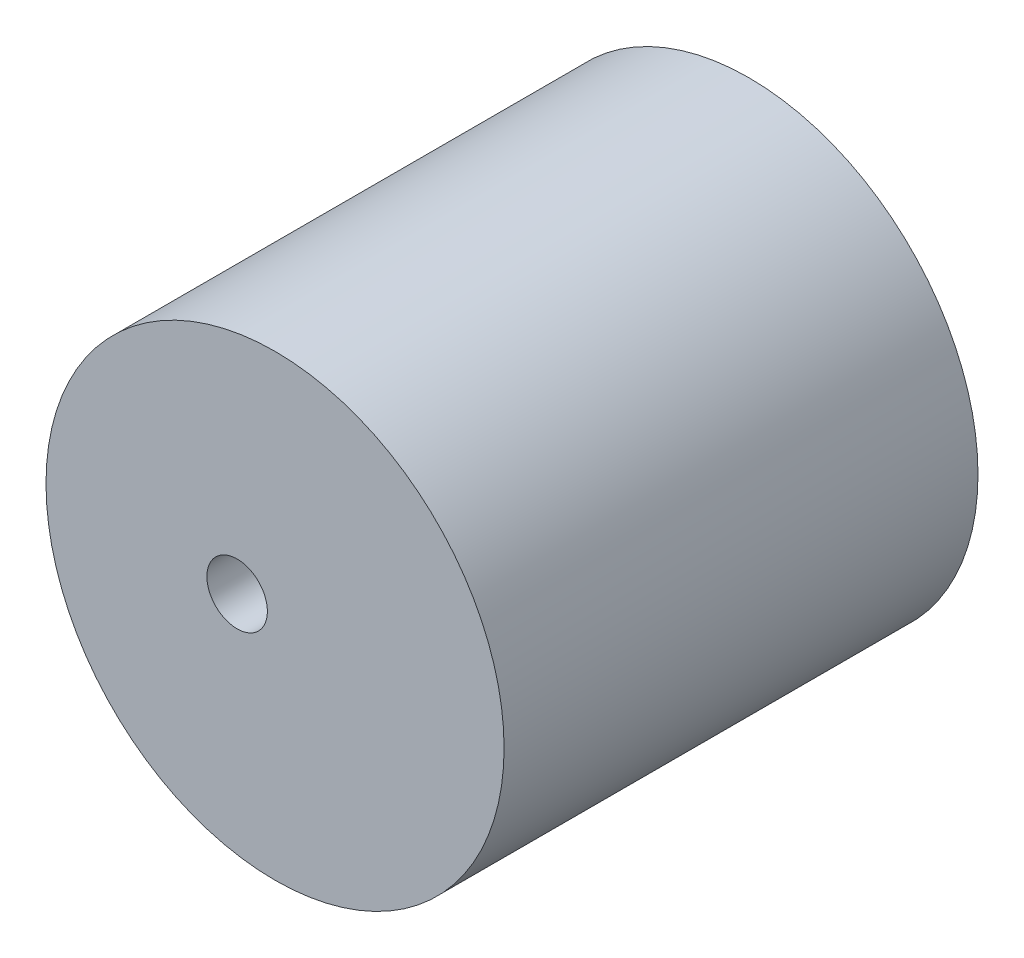
SolidWorks part; units mm, degrees
ref_plane "Front Plane" through (0, 0, 0) normal (0, 0, 1) x (1, 0, 0)
ref_plane "Top Plane" through (0, 0, 0) normal (0, 1, 0) x (1, 0, 0)
ref_plane "Right Plane" through (0, 0, 0) normal (1, 0, 0) x (0, 0, -1)
sketch "Sketch1" plane through (0, 0, 0) normal (0, 0, 1) x (1, 0, 0)
  circle A0 centre (0, 0) radius 24.1656
  circle A2 centre (-4, 0) radius 3.1931
extrude "Boss-Extrude5" add sketch "Sketch1" along normal blind 50 contours A2 | A0 region at (-4, 0, 0)
sketch "Sketch2" plane through (0, 0, 0) normal (0, 0, 1) x (1, 0, 0)
  circle A0 centre (0, 0) radius 23.75
sketch "Sketch3" plane through (0, 0, 0) normal (0, 0, 1) x (1, 0, 0)
  circle A0 centre (-4, 0) radius 3.175
sketch "Sketch4" plane through (0, 0, 0) normal (0, 0, 1) x (1, 0, 0)
  circle A0 centre (0, 0) radius 23.3344
sketch "Sketch5" plane through (0, 0, 0) normal (0, 0, 1) x (1, 0, 0)
  circle A0 centre (0, 0) radius 23.3938
sketch "Sketch6" plane through (0, 0, 0) normal (0, 0, 1) x (1, 0, 0)
  circle A0 centre (0, 0) radius 23.4531
  circle A1 centre (-4, 0) radius 3.2906
extrude "Boss-Extrude9" add sketch "Sketch6" along normal blind 2
sketch "Sketch7" plane through (0, 0, 0) normal (0, 0, 1) x (1, 0, 0)
  circle A0 centre (0, 0) radius 24.1656
  circle A1 centre (-4, 0) radius 3.3069
extrude "Boss-Extrude10" add sketch "Sketch7" along normal blind 2
